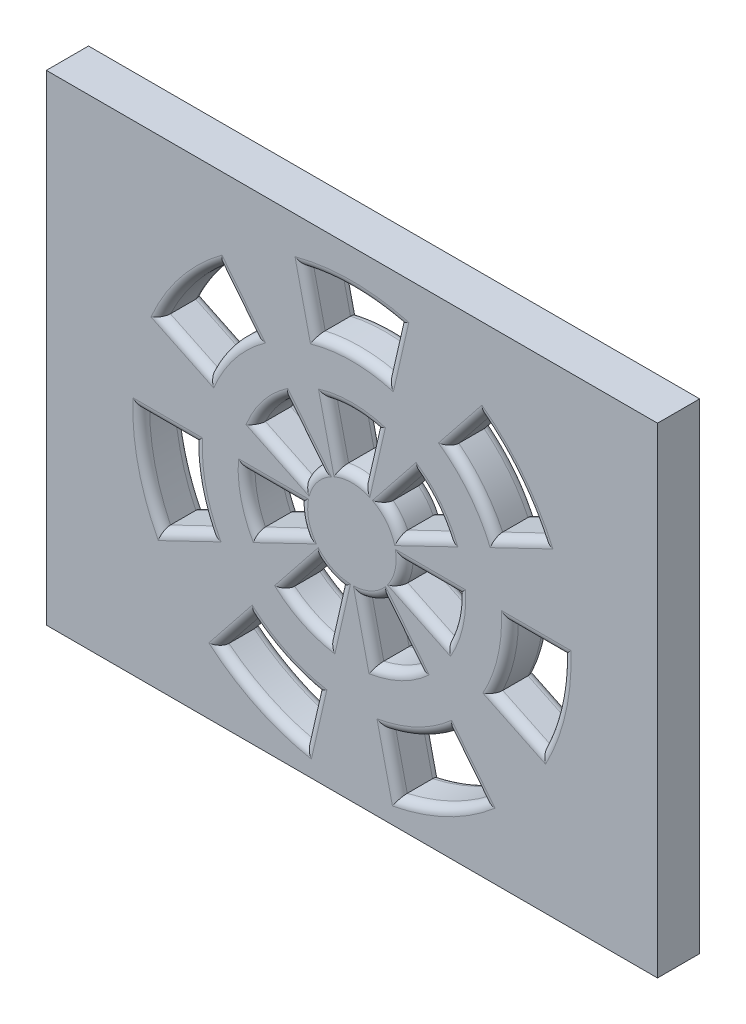
SolidWorks part; units mm, degrees
ref_plane "Front Plane" through (0, 0, 0) normal (0, 0, 1) x (1, 0, 0)
ref_plane "Top Plane" through (0, 0, 0) normal (0, 1, 0) x (1, 0, 0)
ref_plane "Right Plane" through (0, 0, 0) normal (1, 0, 0) x (0, 0, -1)
sketch "Sketch1" plane through (0, 0, 0) normal (0, 1, 0) x (1, 0, 0)
  line L1 (-19.5, 77.5) -> (19.5, 77.5)
  line L2 (-19.5, 77.5) -> (-19.5, -77.5)
  line L3 (-19.5, -77.5) -> (19.5, -77.5)
  line L4 (19.5, 77.5) -> (19.5, -77.5)
  line L5 (-19.5, 77.5) -> (19.5, -77.5) construction
  line L6 (-19.5, -77.5) -> (19.5, 77.5) construction
  point P0 (0, 0)
  dimension "D1" = 39
  dimension "D2" = 155
extrude "Boss-Extrude1" add sketch "Sketch1" along normal blind 2
sketch "Sketch2" plane through (0, 2, 0) normal (0, 1, 0) x (1, 0, 0)
  line L0 (-17.5, -75.5) -> (-17.5, -77.5)
  line L1 (-19.5, 77.5) -> (19.5, 77.5)
  line L2 (-19.5, 77.5) -> (-19.5, -77.5)
  line L3 (-19.5, -77.5) -> (19.5, -77.5)
  line L4 (19.5, 77.5) -> (19.5, -77.5)
  line L5 (-17.5, 75.5) -> (17.5, 75.5)
  line L6 (-17.5, 75.5) -> (-17.5, -75.5)
  line L7 (-17.5, -75.5) -> (17.5, -75.5)
  line L8 (17.5, 75.5) -> (17.5, -75.5)
  line L9 (-17.5, 75.5) -> (17.5, -75.5) construction
  line L10 (-17.5, -75.5) -> (17.5, 75.5) construction
  line L11 (17.5, -75.5) -> (17.5, -77.5)
  point P6 (0, 0)
  line M9 (19.5, -77.5) -> (19.5, 77.5)
  line M10 (19.5, 77.5) -> (-19.5, 77.5)
  line M11 (-19.5, 77.5) -> (-19.5, -77.5)
  line M12 (-19.5, -77.5) -> (19.5, -77.5)
  dimension "D1" = 2
  dimension "D2" = 2
extrude "Boss-Extrude2" add sketch "Sketch2" along normal blind 38 contours L8 L11 L3 L0 L6 L5 M9 M10 M11 M12 region at (-19.0983, 2, 76.5)
sketch "Sketch3" plane through (0, 2, 0) normal (0, 1, 0) x (1, 0, 0)
  line L0 (-17.5, 75.5) -> (-17.5, -77.5) construction
  line L1 (-17.5, -77.5) -> (-15.5, -77.5)
  line L2 (-17.5, -77.5) -> (-17.5, -75.5)
  line L3 (-17.5, -75.5) -> (-15.5, -75.5)
  line L4 (-15.5, -77.5) -> (-15.5, -75.5)
  line L5 (-17.5, -73.3) -> (-15.5, -73.3)
  line L6 (-17.5, -73.3) -> (-17.5, -71.3)
  line L7 (-17.5, -71.3) -> (-15.5, -71.3)
  line L8 (-15.5, -73.3) -> (-15.5, -71.3)
  line L9 (17.5, 75.5) -> (17.5, -77.5) construction
  line L10 (17.5, -77.5) -> (15.5, -77.5)
  line L11 (17.5, -77.5) -> (17.5, -75.5)
  line L12 (17.5, -75.5) -> (15.5, -75.5)
  line L13 (15.5, -77.5) -> (15.5, -75.5)
  line L14 (17.5, -73.3) -> (15.5, -73.3)
  line L15 (17.5, -73.3) -> (17.5, -71.3)
  line L16 (17.5, -71.3) -> (15.5, -71.3)
  line L17 (15.5, -73.3) -> (15.5, -71.3)
  line L18 (15.5, -75.5) -> (15.5, -73.3) construction
  line L19 (-15.5, -73.3) -> (15.5, -73.3) construction
  line L20 (-15.5, -75.5) -> (-15.5, -73.3) construction
  line L21 (-15.5, -75.5) -> (15.5, -75.5) construction
  line L22 (15.5, -71.3) -> (-15.5, -71.3) construction
  dimension "D1" = 2
  dimension "D2" = 2
  dimension "D3" = 2.2
  dimension "D4" = 2
extrude "Boss-Extrude3" add sketch "Sketch3" along normal up to surface (38 mm away) up to face at (0, 40, 0.5)
sketch "Sketch4" plane through (0, 0, -75.5) normal (0, 0, 1) x (1, 0, 0)
  line L0 (-17.5, 40) -> (-15.5, 40)
  line L1 (-17.5, 40) -> (17.5, 40) construction
  line L2 (-15.5, 40) -> (-15.5, 38)
  line L3 (-15.5, 38) -> (-17.5, 38)
  line L5 (-17.5, 38) -> (-17.5, 40)
  line L7 (-17.5, 40) -> (-17.5, 2) construction
  line L8 (-15.5, 33.8) -> (-17.5, 31.8)
  line L9 (-17.5, 31.8) -> (-17.5, 35.8)
  line L10 (-15.5, 33.8) -> (-15.5, 35.8)
  line L11 (-15.5, 35.8) -> (-17.5, 35.8)
  line L12 (0, 0) -> (0, 40) construction
  line L13 (15.5, 35.8) -> (17.5, 35.8)
  line L14 (15.5, 33.8) -> (15.5, 35.8)
  line L15 (17.5, 31.8) -> (17.5, 35.8)
  line L16 (15.5, 33.8) -> (17.5, 31.8)
  line L17 (17.5, 38) -> (17.5, 40)
  line L18 (15.5, 38) -> (17.5, 38)
  line L19 (15.5, 40) -> (15.5, 38)
  line L20 (17.5, 40) -> (15.5, 40)
  dimension "D1" = 2
  dimension "D2" = 2
  dimension "D3" = 45
  dimension "D4" = 2.2
  dimension "D5" = 2
extrude "Boss-Extrude4" add sketch "Sketch4" along normal up to surface (153 mm away) up to face at (0, 20.5, 77.5)
sketch "Sketch5" plane through (0, 2, 0) normal (0, 1, 0) x (1, 0, 0)
  line L1 (-15.5, -77.5) -> (15.5, -77.5)
  line L2 (-15.5, -77.5) -> (-15.5, -75.5)
  line L3 (-15.5, -75.5) -> (15.5, -75.5)
  line L4 (15.5, -77.5) -> (15.5, -75.5)
  line L5 (-15.5, -71.3) -> (15.5, -71.3)
  line L6 (-15.5, -71.3) -> (-15.5, -73.3)
  line L7 (-15.5, -73.3) -> (15.5, -73.3)
  line L8 (15.5, -71.3) -> (15.5, -73.3)
sketch "Sketch6" plane through (0, 0, -75.5) normal (0, 0, 1) x (1, 0, 0)
  line L0 (-17.5, 38) -> (-15.5, 38) construction
  line L1 (-17.5, 38) -> (17.5, 38)
  line L2 (-17.5, 38) -> (-17.5, 35.8)
  line L3 (-17.5, 35.8) -> (17.5, 35.8)
  line L4 (17.5, 38) -> (17.5, 35.8)
  line L5 (-17.5, 38) -> (-17.5, 35.8) construction
  line L6 (-15.5, 35.8) -> (-17.5, 35.8) construction
extrude "Cut-Extrude1" cut sketch "Sketch6" along normal through all
sketch "Sketch7" plane through (0, 2, 0) normal (0, 1, 0) x (1, 0, 0)
  line L1 (-17.5, -75.5) -> (17.5, -75.5)
  line L2 (-17.5, -75.5) -> (-17.5, -73.3)
  line L3 (-17.5, -73.3) -> (17.5, -73.3)
  line L4 (17.5, -75.5) -> (17.5, -73.3)
extrude "Cut-Extrude2" cut sketch "Sketch7" along normal through all
extrude "Boss-Extrude5" add sketch "Sketch5" along normal blind 2
sketch "Sketch8" plane through (0, 0, 0) normal (1, 0, 0) x (0, 0, -1)
  line L0 (75.5, 40) -> (73.5, 40)
  line L1 (-73.3, 40) -> (75.5, 40) construction
  line L2 (73.5, 40) -> (73.5, 38)
  line L3 (-73.3, 38) -> (75.5, 38) construction
  line L4 (73.5, 38) -> (75.5, 38)
  line L5 (75.5, 38) -> (75.5, 40)
  line L6 (75.5, 35.8) -> (73.5, 35.8)
  line L7 (-73.3, 35.8) -> (75.5, 35.8) construction
  line L8 (73.5, 35.8) -> (73.5, 33.8)
  line L9 (-71.3, 33.8) -> (75.5, 33.8) construction
  line L10 (73.5, 33.8) -> (75.5, 31.8)
  line L11 (75.5, 31.8) -> (75.5, 35.8)
  dimension "D1" = 2
extrude "Boss-Extrude6" add sketch "Sketch8" along normal up to surface and the other way up to surface up to face at (17.5, 16.9, -2.1) other way up to face at (-17.5, 16.9, -2.1)
sketch "Sketch10" plane through (-17.5, 0, 0) normal (1, 0, 0) x (0, 0, -1)
  line L1 (-75.5, 35.8) -> (-77.5, 35.8)
  line L2 (-75.5, 35.8) -> (-75.5, 38)
  line L3 (-75.5, 38) -> (-77.5, 38)
  line L4 (-77.5, 35.8) -> (-77.5, 38)
  line L5 (-73.3, 40) -> (-75.5, 40)
  line L6 (-73.3, 40) -> (-73.3, 38)
  line L7 (-73.3, 38) -> (-75.5, 38)
  line L8 (-75.5, 40) -> (-75.5, 38)
  line M1 (-75.5, 40) -> (-75.5, 38)
  line M2 (-75.5, 38) -> (-77.5, 38)
  line M3 (-77.5, 38) -> (-77.5, 35.8)
  line M4 (-77.5, 35.8) -> (-75.5, 35.8)
  line M11 (-73.3, 38) -> (-73.3, 40)
  line M12 (-73.3, 40) -> (-75.5, 40)
extrude "Boss-Extrude8" add sketch "Sketch10" along normal up to surface (2 mm away) contours L2 M4 M2 M3 | L7 M11 M12 M1 region at (-17.5, 39, 74.4) region at (-17.5, 36.9, 76.5) up to face at (-15.5, 39, -0.1)
sketch "Sketch11" plane through (17.5, 0, 0) normal (-1, 0, 0) x (0, 0, 1)
  line L1 (75.5, 35.8) -> (77.5, 35.8)
  line L2 (75.5, 35.8) -> (75.5, 38)
  line L3 (75.5, 38) -> (77.5, 38)
  line L4 (77.5, 35.8) -> (77.5, 38)
  line L5 (73.3, 40) -> (75.5, 40)
  line L6 (73.3, 40) -> (73.3, 38)
  line L7 (73.3, 38) -> (75.5, 38)
  line L8 (75.5, 40) -> (75.5, 38)
  line M2 (75.5, 35.8) -> (77.5, 35.8)
  line M3 (77.5, 35.8) -> (77.5, 38)
  line M4 (77.5, 38) -> (75.5, 38)
  line M5 (75.5, 38) -> (75.5, 40)
  line M6 (75.5, 40) -> (73.3, 40)
  line M7 (73.3, 40) -> (73.3, 38)
extrude "Boss-Extrude9" add sketch "Sketch11" along normal up to surface (2 mm away) contours L2 M2 M3 M4 | L7 M7 M5 M6 region at (17.5, 36.9, 76.5) region at (17.5, 39, 74.4) up to face at (15.5, 39, -0.1)
fillet "Fillet2" radius 2.5 17 edges at (-17.5, 16.9, 71.3) (17.5, 16.9, 71.3) (19.5, 20, 77.5) (-19.5, 20, 77.5) (-19.5, 20, -77.5) (-17.5, 16.9, -75.5) (17.5, 16.9, -75.5) (19.5, 20, -77.5) (-19.5, 40, 0) (0, 40, -77.5) (19.5, 40, 0) (0, 0, -77.5) (0, 0, 77.5) (-19.5, 0, 0) (19.5, 0, 0) (-17.5, 40, 77.5) (17.5, 40, 77.5)
sketch "Sketch13" plane through (0, 0, -77.5) normal (0, 0, -1) x (-1, 0, 0)
  line L0 (15.5, 37.5) -> (15.5, 4) construction
  line L1 (-15.5, 7) -> (15.5, 7)
  line L2 (-15.5, 7) -> (-15.5, 4)
  line L3 (-15.5, 4) -> (15.5, 4)
  line L4 (15.5, 7) -> (15.5, 4)
  dimension "D1" = 3
sketch "Sketch14" plane through (0, 0, -75.5) normal (0, 0, 1) x (1, 0, 0)
  line L1 (-18.25, 9) -> (18.25, 9)
  line L2 (-18.25, 9) -> (-18.25, 1.25)
  line L3 (-18.25, 1.25) -> (18.25, 1.25)
  line L4 (18.25, 9) -> (18.25, 1.25)
  line L5 (15.5, 7) -> (-15.5, 7) construction
  line L7 (17, 0) -> (17, 2.5) construction
  line L8 (19.5, 2.5) -> (17, 2.5) construction
  line L10 (-19.5, 2.5) -> (-17, 2.5) construction
  point P20 (17, 1.25)
  point P23 (18.25, 2.5)
  point P26 (-18.25, 2.5)
  dimension "D1" = 2
extrude "Boss-Extrude10" add sketch "Sketch14" along normal blind 2
extrude "Cut-Extrude4" cut sketch "Sketch13" against normal blind 2
fillet "Fillet3" radius 2 1 edges at (0, 9, -73.5)
fillet "Fillet4" radius 0.5 12 edges at (0, 4, -77.5) (0, 7, -77.5) (15.5, 7, -76.5) (15.5, 4, -76.5) (15.5, 5.5, -77.5) (-15.5, 4, -76.5) (-15.5, 7, -76.5) (-15.5, 5.5, -77.5) (0, 7, -75.5) (-15.5, 5.5, -75.5) (0, 4, -75.5) (15.5, 5.5, -75.5)
sketch "Sketch15" plane through (0, 0, 0) normal (0, -1, 0) x (1, 0, 0)
  line L0 (0, 77.5) -> (0, 0) construction
  line L1 (-17, 77.5) -> (17, 77.5) construction
  line L2 (0, 0) -> (0, -77.5) construction
  line L4 (17, -77.5) -> (-17, -77.5) construction
  circle A0 centre (0, 38.75) radius 5.1
  circle A1 centre (0, -38.75) radius 5.1
  dimension "D1" = 10.2
extrude "Cut-Extrude5" cut sketch "Sketch15" against normal through all
sketch "Sketch16" plane through (0, 2, 0) normal (0, 1, 0) x (1, 0, 0)
  circle A0 centre (0, 38.75) radius 7.1
  circle A1 centre (0, -38.75) radius 7.1
  circle A2 centre (0, 38.75) radius 5.1 construction
  dimension "D1" = 2
extrude "Boss-Extrude11" add sketch "Sketch16" along normal blind 1
fillet "Fillet5" radius 0.5 4 edges at (0, 2, 45.85) (0, 2, -31.65) (0, 3, 45.85) (0, 3, -31.65)
sketch "Sketch12" plane through (0, 0, -75.5) normal (0, 0, 1) x (1, 0, 0)
  line L0 (0, 0) -> (0, 40) construction
  line L1 (15.5, 40) -> (-15.5, 40) construction
  line L2 (0, 20) -> (-10, 20)
  line L3 (0, 20) -> (-9.0097, 15.6612)
  line L4 (0, 20) -> (-6.2349, 12.1817)
  line L5 (0, 20) -> (-2.2252, 10.2507)
  line L6 (0, 20) -> (2.2252, 10.2507)
  line L7 (0, 20) -> (6.2349, 12.1817)
  line L8 (0, 20) -> (9.0097, 15.6612)
  line L9 (0, 20) -> (10, 20)
  line L10 (0, 20) -> (9.0097, 24.3388)
  line L11 (0, 20) -> (6.2349, 27.8183)
  line L12 (0, 20) -> (2.2252, 29.7493)
  line L13 (0, 20) -> (-2.2252, 29.7493)
  line L14 (0, 20) -> (-6.2349, 27.8183)
  line L15 (0, 20) -> (-9.0097, 24.3388)
  circle A0 centre (0, 20) radius 10
  circle A1 centre (0, 20) radius 7.5
  circle A2 centre (0, 20) radius 5
  circle A3 centre (0, 20) radius 2.5
  point P26 (0, 20)
  dimension "D1" = 20
  dimension "D2" = 2.5
  dimension "D3" = 2.5
  dimension "D4" = 2.5
  dimension "D5" = 14
extrude "Cut-Extrude3" cut sketch "Sketch12" against normal through all contours A1 L6 A0 L7 | A1 L4 A0 L5 | A1 L2 A0 L3 | A1 L14 A0 L15 | A1 L0 A0 L13 | L0 A1 L12 A0 | A1 L10 A0 L11 | A1 L8 A0 L9 | A3 L8 A2 L9 | A3 L10 A2 L11 | L0 A3 L12 A2 | A3 L0 A2 L13 | A3 L14 A2 L15 | A3 L2 A2 L3 | A3 L4 A2 L5 | A3 L6 A2 L7 region at (-3.7903, 12.1293, -75.5) region at (3.7903, 12.1293, -75.5) region at (-1.6732, 16.5256, -75.5) region at (1.6732, 16.5256, -75.5) region at (-8.5168, 18.0561, -75.5) region at (8.5168, 18.0561, -75.5) region at (-0.4345, 23.8563, -75.5) region at (0.4345, 23.8563, -75.5) region at (-3.7596, 19.1419, -75.5) region at (3.7596, 19.1419, -75.5) region at (3.015, 22.4044, -75.5) region at (-3.015, 22.4044, -75.5) region at (-6.8299, 25.4467, -75.5) region at (6.8299, 25.4467, -75.5) region at (-0.9843, 28.7358, -75.5) region at (0.9843, 28.7358, -75.5)
fillet "Fillet6" radius 0.4 112 edges at (5.4555, 26.841, -77.5) (7.8183, 26.2349, -77.5) (7.8835, 23.7965, -77.5) (5.8637, 24.6762, -77.5) (3.75, 20, -77.5) (4.8746, 18.8874, -77.5) (3.3786, 18.3729, -77.5) (2.4373, 19.4437, -77.5) (-1.9471, 28.5306, -77.5) (0, 30, -77.5) (1.9471, 28.5306, -77.5) (0, 27.5, -77.5) (-7.8835, 16.2035, -77.5) (-9.7493, 17.7748, -77.5) (-8.75, 20, -77.5) (-7.312, 18.3311, -77.5) (2.3381, 17.0681, -77.5) (2.1694, 15.4952, -77.5) (0.8345, 16.344, -77.5) (1.0847, 17.7476, -77.5) (-0.8345, 16.344, -77.5) (-2.1694, 15.4952, -77.5) (-2.3381, 17.0681, -77.5) (-1.0847, 17.7476, -77.5) (5.4555, 13.159, -77.5) (4.3388, 10.9903, -77.5) (1.9471, 11.4694, -77.5) (3.2541, 13.2427, -77.5) (0, 22.5, -77.5) (-0.8345, 23.656, -77.5) (0, 25, -77.5) (0.8345, 23.656, -77.5) (-3.3786, 21.6271, -77.5) (-3.9092, 23.1174, -77.5) (-2.3381, 22.9319, -77.5) (-1.9546, 21.5587, -77.5) (-3.3786, 18.3729, -77.5) (-4.8746, 18.8874, -77.5) (-3.75, 20, -77.5) (-2.4373, 19.4437, -77.5) (-1.9471, 11.4694, -77.5) (-4.3388, 10.9903, -77.5) (-5.4555, 13.159, -77.5) (-3.2541, 13.2427, -77.5) (-7.8835, 23.7965, -77.5) (-7.8183, 26.2349, -77.5) (-5.4555, 26.841, -77.5) (-5.8637, 24.6762, -77.5) (2.3381, 22.9319, -77.5) (3.9092, 23.1174, -77.5) (3.3786, 21.6271, -77.5) (1.9546, 21.5587, -77.5) (8.75, 20, -77.5) (9.7493, 17.7748, -77.5) (7.8835, 16.2035, -77.5) (7.312, 18.3311, -77.5) (7.8835, 23.7965, -75.5) (7.8183, 26.2349, -75.5) (5.4555, 26.841, -75.5) (5.8637, 24.6762, -75.5) (3.3786, 18.3729, -75.5) (4.8746, 18.8874, -75.5) (3.75, 20, -75.5) (2.4373, 19.4437, -75.5) (1.9471, 28.5306, -75.5) (0, 30, -75.5) (-1.9471, 28.5306, -75.5) (0, 27.5, -75.5) (-8.75, 20, -75.5) (-9.7493, 17.7748, -75.5) (-7.8835, 16.2035, -75.5) (-7.312, 18.3311, -75.5) (0.8345, 16.344, -75.5) (2.1694, 15.4952, -75.5) (2.3381, 17.0681, -75.5) (1.0847, 17.7476, -75.5) (-2.3381, 17.0681, -75.5) (-2.1694, 15.4952, -75.5) (-0.8345, 16.344, -75.5) (-1.0847, 17.7476, -75.5) (1.9471, 11.4694, -75.5) (4.3388, 10.9903, -75.5) (5.4555, 13.159, -75.5) (3.2541, 13.2427, -75.5) (0, 22.5, -75.5) (0.8345, 23.656, -75.5) (0, 25, -75.5) (-0.8345, 23.656, -75.5) (-2.3381, 22.9319, -75.5) (-3.9092, 23.1174, -75.5) (-3.3786, 21.6271, -75.5) (-1.9546, 21.5587, -75.5) (-3.75, 20, -75.5) (-4.8746, 18.8874, -75.5) (-3.3786, 18.3729, -75.5) (-2.4373, 19.4437, -75.5) (-5.4555, 13.159, -75.5) (-4.3388, 10.9903, -75.5) (-1.9471, 11.4694, -75.5) (-3.2541, 13.2427, -75.5) (-5.4555, 26.841, -75.5) (-7.8183, 26.2349, -75.5) (-7.8835, 23.7965, -75.5) (-5.8637, 24.6762, -75.5) (3.3786, 21.6271, -75.5) (3.9092, 23.1174, -75.5) (2.3381, 22.9319, -75.5) (7.8835, 16.2035, -75.5) (9.7493, 17.7748, -75.5) (8.75, 20, -75.5) (7.312, 18.3311, -75.5) (1.9546, 21.5587, -75.5)
fillet "Fillet7" radius 0.5 8 edges at (15.5, 40, 0.75) (15.5, 39.2678, 76.7678) (-15.5, 40, 0.75) (-15.5, 39.2678, 76.7678) (0, 40, -73.5) (15.5, 20.75, 77.5) (-15.5, 20.75, 77.5) (0, 4, 77.5)
sketch "Sketch17" plane through (0, 0, 0) normal (0, -1, 0) x (1, 0, 0)
  line L0 (-17, -77.5) -> (-17, 70.3)
  line L1 (-17, -77.5) -> (17, -77.5)
  line L2 (17, -77.5) -> (17, 70.3)
  line L3 (17, -75) -> (17, 75) construction
  line L5 (17, 70.3) -> (15, 71.3)
  line L6 (15, 71.3) -> (15, 77.5)
  line L7 (15, 77.5) -> (-15, 77.5)
  line L8 (-15, 77.5) -> (-15, 71.3)
  line L9 (-15, 71.3) -> (-17, 70.3)
  line L10 (-17, 75) -> (-17, -75) construction
  line L12 (-15, 71.3) -> (15, 71.3) construction
  line L13 (17, 70.3) -> (-17, 70.3) construction
  line L14 (0, 71.3) -> (0, 77.5) construction
  line L15 (-17, 77.5) -> (17, 77.5) construction
  arc A0 (-19.5, -75) -> (-17, -77.5) centre (-17, -75) ccw construction
  dimension "D1" = 1
  dimension "D2" = 30
  dimension "D3" = 6.2
extrude "Cut-Extrude6" cut sketch "Sketch17" against normal blind 6
sketch "Sketch18" plane through (0, 0, 0) normal (0, 0, 1) x (1, 0, 0)
  line L0 (15, 9) -> (-15, 9) construction
  line L1 (-14.5, 9) -> (14.5, 9)
  line L2 (-14.5, 9) -> (-14.5, 6)
  line L3 (-14.5, 6) -> (14.5, 6)
  line L4 (14.5, 9) -> (14.5, 6)
  line L5 (-17, 6) -> (17, 6) construction
  line L6 (0, 6) -> (0, 0) construction
  dimension "D1" = 29
extrude "Cut-Extrude8" cut sketch "Sketch18" against normal through all
sketch "Sketch20" plane through (0, 0, 0) normal (0, 0, 1) x (1, 0, 0)
  line L0 (-16, 40) -> (16, 40) construction
  line L1 (-19.5, 40) -> (-14.5, 40)
  line L2 (-19.5, 40) -> (-19.5, 0)
  line L3 (-19.5, 0) -> (-14.5, 0)
  line L4 (-14.5, 40) -> (-14.5, 0)
  line L5 (-14.5, 6) -> (14.5, 6)
  line L6 (-14.5, 6) -> (-14.5, 40)
  line L7 (-14.5, 40) -> (14.5, 40)
  line L8 (14.5, 6) -> (14.5, 40)
  line L9 (14.5, 40) -> (19.5, 40)
  line L10 (14.5, 40) -> (14.5, 0)
  line L11 (14.5, 0) -> (19.5, 0)
  line L12 (19.5, 40) -> (19.5, 0)
  line L13 (-15, 0) -> (-17, 0) construction
  line L14 (-19.5, 2.5) -> (-19.5, 37.5) construction
  line L15 (17, 0) -> (15, 0) construction
  line L16 (19.5, 37.5) -> (19.5, 2.5) construction
extrude "Cut-Extrude11" cut sketch "Sketch20" against normal through all both and the other way through all contours L12 L9 L8 L10 L11 | L1 L2 L3 L4 region at (17, 20, 0)
sketch "Sketch21" plane through (0, 0, -75.5) normal (0, 0, 1) x (1, 0, 0)
  line L1 (-14.5, 31.8) -> (14.5, 31.8)
  line L2 (-14.5, 31.8) -> (-14.5, 40)
  line L3 (-14.5, 40) -> (14.5, 40)
  line L4 (14.5, 31.8) -> (14.5, 40)
  line L5 (14.5, 31.8) -> (-14.5, 31.8)
  line L6 (14.5, 31.8) -> (14.5, 9)
  line L7 (14.5, 9) -> (-14.5, 9)
  line L8 (-14.5, 31.8) -> (-14.5, 9)
extrude "Cut-Extrude12" cut sketch "Sketch21" against normal through all both and the other way through all contours L1 L4 L3 L2 region at (0, 35.9, -75.5)
